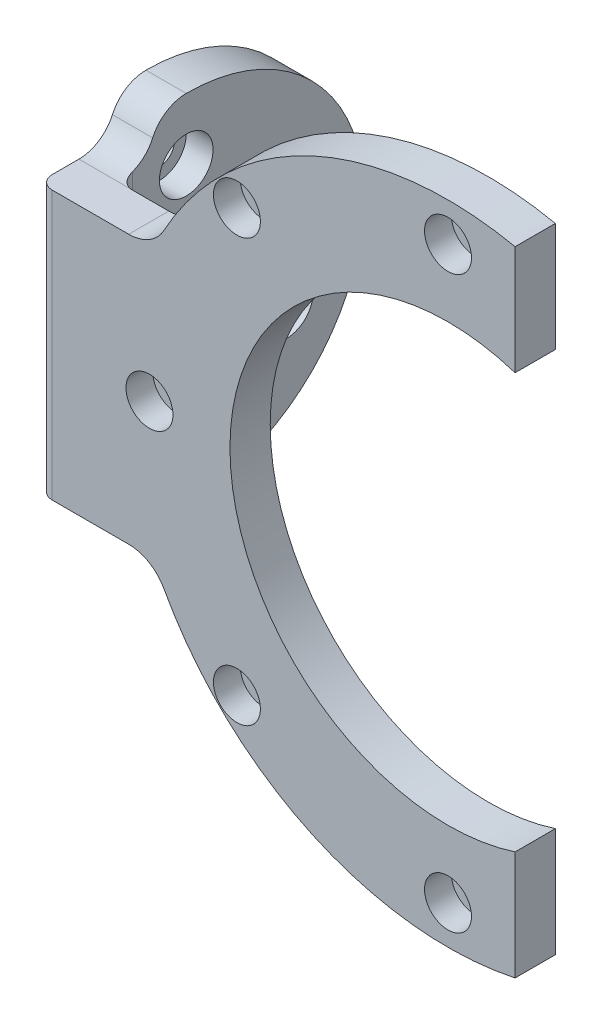
SolidWorks part; units mm, degrees
ref_plane "前视基准面" through (0, 0, 0) normal (0, 0, 1) x (1, 0, 0)
ref_plane "上视基准面" through (0, 0, 0) normal (0, 1, 0) x (1, 0, 0)
ref_plane "右视基准面" through (0, 0, 0) normal (1, 0, 0) x (0, 0, -1)
sketch "草图3" plane through (0, 0, 0) normal (0, 0, 1) x (1, 0, 0)
  circle A0 centre (0, 0) radius 32.5
  circle A1 centre (0, 0) radius 48.25
  dimension "D1" = 65
  dimension "D2" = 96.5
extrude "凸台-拉伸2" add sketch "草图3" along normal blind 3
ref_plane "基准面5" through (0, 0, 3) normal (0, 0, 1) x (1, 0, 0)
sketch "草图5" plane through (0, 0, 3) normal (0, 0, 1) x (1, 0, 0)
  circle A0 centre (0, 0) radius 39.1975
  circle A1 centre (0, 0) radius 41.5253
extrude "凸台-拉伸3" add sketch "草图5" against normal blind 0.1
sketch "草图2" plane through (0, 0, 0) normal (0, 0, 1) x (1, 0, 0)
  circle A0 centre (0, 0) radius 32.5
  circle A1 centre (0, 0) radius 48.25
  circle A4 centre (0, 0) radius 32.5 construction
  circle A5 centre (0, 0) radius 48.25
  circle A6 centre (0, 0) radius 48.25
  dimension "D1" = 0
extrude "凸台-拉伸1" add sketch "草图2" against normal blind 3 contours A1 A0 region at (-46.8853, 0, 0)
sketch "草图8" plane through (0, 0, 0) normal (0, 0, 1) x (1, 0, 0)
  line L6 (-57, 20.0109) -> (-47.5925, 20.0109)
  line L8 (1.65, 0) -> (-1.65, 0) construction
  line L10 (-57, 20.0109) -> (-57, -20.0109)
  line L11 (-57, -20.0109) -> (-47.5925, -20.0109)
  arc A16 (-47.5925, 20.0109) -> (-42.3489, 23.1222) centre (-47.5925, 25.9853) ccw
  arc A17 (-42.3489, 23.1222) -> (-42.3489, -23.1222) centre (0, 0) ccw
  arc A19 (-47.5925, -20.0109) -> (-42.3489, -23.1222) centre (-47.5925, -25.9853) cw
  circle A20 centre (0, 0) radius 48.25 construction
  dimension "D1" = 57
extrude "凸台-拉伸5" add sketch "草图8" along normal blind 3 and the other way blind 2.98
sketch "草图31" plane through (0, 0, 3) normal (0, 0, 1) x (1, 0, 0)
  circle A0 centre (0, 0) radius 44.5 construction
  circle A1 centre (0, 44.5) radius 2
  circle A2 centre (31.4663, 31.4663) radius 2
  circle A3 centre (44.5, 0) radius 2
  circle A4 centre (31.4663, -31.4663) radius 2
  circle A5 centre (0, -44.5) radius 2
  circle A6 centre (-31.4663, -31.4663) radius 2
  circle A7 centre (-44.5, 0) radius 2
  circle A8 centre (-31.4663, 31.4663) radius 2
  circle A9 centre (0, 0) radius 42.5
  circle A10 centre (0, 42.5) radius 2
  circle A11 centre (0, -42.5) radius 2
  point P21 (0, 0)
  dimension "D1" = 89
  dimension "D2" = 4
  dimension "D4" = 85
  dimension "D5" = 4
  dimension "D6" = 4
  dimension "D3" = 8
hole_wizard "M3.5 螺纹孔的螺纹孔钻头1" positions "3D草图3" profile "草图12" hole size "M3.5" standard "ISO" end condition through all
sketch3d "3D草图3"
  point P118 (31.4663, 31.4663, 3)
  point P121 (44.5, 0, 3)
  point P124 (31.4663, -31.4663, 3)
  point P130 (-31.4663, -31.4663, 3)
  point P133 (-44.5, 0, 3)
  point P136 (-31.4663, 31.4663, 3)
  point P139 (0, -42.5, 3)
  point P142 (0, 42.5, 3)
sketch "草图12" plane through (31.4663, 31.4663, 3) normal (1, 0, 0) x (0, -1, 0)
  line L0 (0, 0) -> (0, 6)
  line L1 (0, 6) -> (1.45, 6)
  line L2 (1.45, 6) -> (1.45, 0)
  line L5 (1.45, 0) -> (0, 0)
  line L11 (0, -6.35) -> (0, 107.95) construction
  dimension "通孔孔直径" = 2.9
  dimension "通孔孔深度" = 6
ref_plane "基准面6" through (-57, 0, 0) normal (-1, 0, 0) x (0, 0, 1)
sketch "草图26" plane through (-57, 0, 0) normal (-1, 0, 0) x (0, 0, 1)
  line L1 (-2.98, -20.008) -> (3, -20.008)
  line L5 (3, 20.0109) -> (3, -20.0109) construction
  line L6 (-2.98, 20.0109) -> (3, 20.0109)
  line L8 (3, 20.0109) -> (3, -20.008)
  line L9 (-2.98, -20.008) -> (3, -20.008)
  arc A8 (-12.98, 26.5) -> (-12.98, -26.5) centre (-12.98, 0) ccw
  arc A9 (-12.98, 26.5) -> (-7.98, 23.254) centre (-12.9844, 21.0193) cw
  arc A10 (-2.98, 20.0109) -> (-7.98, 23.254) centre (-2.98, 25.4867) cw
  arc A11 (-2.98, -20.008) -> (-7.98, -23.254) centre (-2.98, -25.4819) ccw
  arc A12 (-12.98, -26.5) -> (-7.98, -23.254) centre (-12.98, -21.0261) ccw
extrude "凸台-拉伸7" add sketch "草图26" along normal blind 4 and the other way blind 2 contours A8 A12 A11 L1 L8 L6 A10 A9 region at (-57, 0.0002, -16.9155)
sketch "草图27" plane through (0, 0, 0) normal (0, 0, 1) x (1, 0, 0)
  line L2 (10, -47.2024) -> (10, 47.2024)
  arc A1 (10, 47.2024) -> (10, -47.2024) centre (0, 0) cw
  circle A2 centre (0, 0) radius 48.25 construction
  arc A3 (-42.3489, -23.1222) -> (-42.3489, 23.1222) centre (0, 0) ccw construction
  dimension "D1" = 10
extrude "切除-拉伸10" cut sketch "草图27" against normal through all both and the other way through all
sketch "草图32" plane through (-55, 0, 0) normal (1, 0, 0) x (0, 0, -1)
  circle A0 centre (12.98, 0) radius 17.25 construction
  circle A1 centre (12.98, 17.25) radius 2
  circle A2 centre (27.9189, 8.625) radius 2
  circle A3 centre (27.9189, -8.625) radius 2
  circle A4 centre (12.98, -17.25) radius 2
  circle A5 centre (-1.9589, -8.625) radius 2
  circle A6 centre (-1.9589, 8.625) radius 2
  point P17 (12.98, 0)
  dimension "D1" = 34.5
  dimension "D2" = 4
hole_wizard "M4 六角凹头盖的柱孔3" positions "3D草图5" profile "草图29" counterbore size "M4" standard "BSI" end condition up to next
sketch3d "3D草图5"
  point P67 (-55, 17.25, -12.98)
  point P70 (-55, 8.625, -27.9189)
  point P73 (-55, -8.625, -27.9189)
  point P76 (-55, -17.25, -12.98)
sketch "草图29" plane through (-55, 17.25, -12.98) normal (0, 1, 0) x (0, 0, -1)
  line L0 (0, 0) -> (0, 6)
  line L1 (0, 6) -> (2.25, 6)
  line L3 (2.25, 6) -> (2.25, 4)
  line L4 (2.25, 4) -> (4, 4)
  line L5 (4, 4) -> (4, 0)
  line L7 (4, 0) -> (0, 0)
  line L11 (0, -6.35) -> (0, 107.95) construction
  dimension "通孔孔直径" = 4.5
  dimension "通孔孔深度" = 6
  dimension "柱形沉头孔直径" = 8
  dimension "柱形沉头孔深度" = 4
fillet "圆角1" radius 2 1 edges at (-61, 0.0014, 3)
sketch "草图30" plane through (-57, 0, 0) normal (-1, 0, 0) x (0, 0, 1)
  line L1 (-12.98, 8.3917) -> (-12.98, -8.3917)
  arc A7 (-12.98, -8.3917) -> (-12.98, 8.3917) centre (-12.98, 0) cw
extrude "切除-拉伸11" cut sketch "草图30" along normal blind 10 and the other way blind 10
fillet "圆角2" radius 3 2 edges at (-58, -8.3917, -12.98) (-58, 8.3917, -12.98)
sketch "草图33" plane through (0, 0, 3) normal (0, 0, 1) x (1, 0, 0)
  circle A0 centre (0, 42.5) radius 3.5
  circle A1 centre (0, -42.5) radius 3.5
  circle A2 centre (-31.4663, 31.4663) radius 3.5
  circle A3 centre (-44.5, 0) radius 3.5
  circle A4 centre (-31.4663, -31.4663) radius 3.5
  point P8 (0, 0)
  point P16 (0, 0)
  dimension "D1" = 7
  dimension "D3" = 7
  dimension "D2" = 2
  dimension "D4" = 3
extrude "切除-拉伸12" cut sketch "草图33" against normal blind 4
fillet "圆角5" radius 2 1 edges at (-55, 0.0014, -2.98)
sketch "草图34" plane through (0, 0, 3) normal (0, 0, 1) x (1, 0, 0)
  line L0 (10, -30.9233) -> (10, 30.9233)
  line L1 (10, 30.9233) -> (10, 48.9898)
  line L2 (10, -30.9233) -> (10, -48.9898)
  circle A0 centre (0, 0) radius 50
  circle A1 centre (0, 0) radius 48
  arc M9 (-47.5925, -20.0109) -> (-42.3489, -23.1222) centre (-47.5925, -25.9853) cw
  arc M10 (-42.3489, -23.1222) -> (10, -47.2024) centre (0, 0) ccw
  line M11 (10, -47.2024) -> (10, -30.9233)
  arc M14 (10, 47.2024) -> (-42.3489, 23.1222) centre (0, 0) ccw
  arc M15 (-42.3489, 23.1222) -> (-47.5925, 20.0109) centre (-47.5925, 25.9853) cw
  dimension "D1" = 2
  dimension "D2" = 96
extrude "凸台-拉伸8" [suppressed] add sketch "草图34" against normal up to surface (6 mm away) contours L1 A0 M15 M14 | A1 L1 A0 M14 M15 M9 M10 M11 | A0 L2 M9 M10
fillet "圆角3" [suppressed] radius 10
sketch "草图36" plane through (0, 0, -2.98) normal (0, 0, -1) x (-1, 0, 0)
  line L5 (53, 20.0109) -> (47.5925, 20.0109)
  line L6 (47.5925, -20.0109) -> (57, -20.0109)
  line L7 (57, -20.0109) -> (57, -20.008)
  line L8 (57, -20.008) -> (53, -20.008)
  line L9 (53, -20.008) -> (53, 20.0109)
  line L10 (53, 20.0109) -> (47.5925, 20.0109)
  line L11 (47.5925, -20.0109) -> (57, -20.0109)
  line L12 (57, -20.0109) -> (57, -20.008)
  line L13 (57, -20.008) -> (53, -20.008)
  line L15 (53, -20.008) -> (53, 20.0109)
  arc A3 (42.3489, 23.1222) -> (47.5925, 20.0109) centre (47.5925, 25.9853) ccw
  arc A4 (42.3489, 23.1222) -> (47.5925, 20.0109) centre (47.5925, 25.9853) ccw
  arc A5 (42.3489, -23.1222) -> (42.3489, 23.1222) centre (0, 0) ccw
  arc A9 (42.3489, -23.1222) -> (42.3489, 23.1222) centre (0, 0) ccw
  arc A10 (47.5925, -20.0109) -> (42.3489, -23.1222) centre (47.5925, -25.9853) ccw
  arc A11 (47.5925, -20.0109) -> (42.3489, -23.1222) centre (47.5925, -25.9853) ccw
  dimension "D1" = 0
extrude "凸台-拉伸9" [suppressed] add sketch "草图36" along normal up to surface (0.02 mm away)
fillet "圆角4" [suppressed] radius 2
